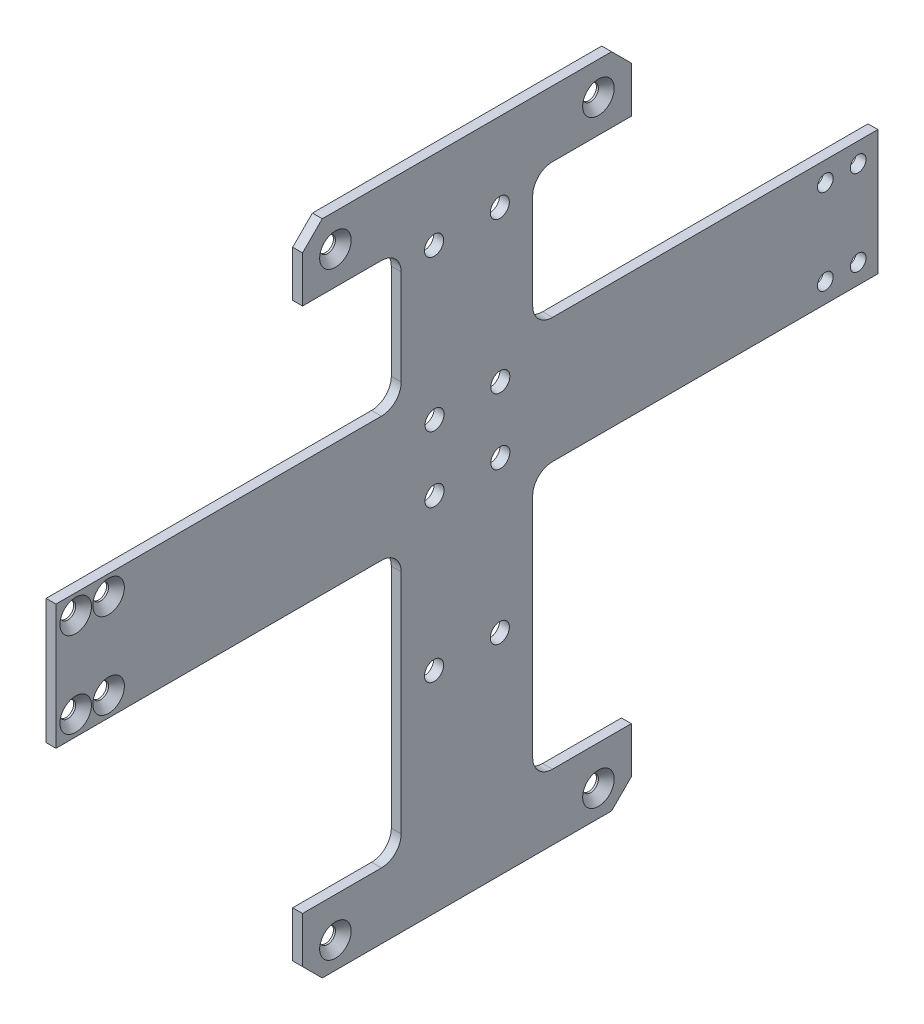
SolidWorks part; units mm, degrees
material "Hexcel AS4C (3000 Filaments)"
ref_plane "Front Plane" through (0, 0, 0) normal (0, 0, 1) x (1, 0, 0)
ref_plane "Top Plane" through (0, 0, 0) normal (0, 1, 0) x (1, 0, 0)
ref_plane "Right Plane" through (0, 0, 0) normal (1, 0, 0) x (0, 0, -1)
sketch "Sketch1" plane through (0, 0, 0) normal (0, 0, 1) x (1, 0, 0)
  line L1 (0.75, -12.5) -> (-0.75, -12.5)
  line L2 (0.75, -12.5) -> (0.75, 12.5)
  line L3 (0.75, 12.5) -> (-0.75, 12.5)
  line L4 (-0.75, -12.5) -> (-0.75, 12.5)
  line L5 (0.75, -12.5) -> (-0.75, 12.5) construction
  line L6 (0.75, 12.5) -> (-0.75, -12.5) construction
  point P0 (0, 0)
  dimension "D1" = 1.5
  dimension "D2" = 25
extrude "Boss-Extrude1" add sketch "Sketch1" along normal blind 73 and the other way blind 73
fillet "Fillet1" radius 1 4 edges at (0, -12.5, 73) (0, 12.5, 73) (0, -12.5, -73) (0, 12.5, -73)
sketch "Sketch10" plane through (0, 0, 0) normal (1, 0, 0) x (0, 0, -1)
  line L0 (72, 12.5) -> (-72, 12.5) construction
  line L1 (-10, 12.5) -> (10, 12.5)
  line L2 (-10, 12.5) -> (-10, 37.5)
  line L3 (-10, 37.5) -> (10, 37.5)
  line L4 (10, 12.5) -> (10, 37.5)
  line L5 (0, 0) -> (0, 37.5) construction
  dimension "D1" = 20
  dimension "D2" = 25
extrude "Boss-Extrude2" add sketch "Sketch10" along normal up to surface and the other way up to surface up to face at (0.75, 0, 0) other way up to face at (-0.75, 0, 0)
sketch "Sketch16" plane through (-0.75, 0, 0) normal (-1, 0, 0) x (0, 0, 1)
  line L0 (-72, 12.5) -> (-10, 12.5) construction
  line L1 (-73, 9.5) -> (-32.5, 9.5)
  line L2 (-73, 9.5) -> (-73, 12.5)
  line L3 (-73, 12.5) -> (-32.5, 12.5)
  line L4 (-32.5, 9.5) -> (-32.5, 12.5)
  line L5 (-73, 11.5) -> (-73, -11.5) construction
  line L6 (0, 0) -> (-20.9009, 0) construction
  line L7 (-32.5, -9.5) -> (-32.5, -12.5)
  line L8 (-73, -12.5) -> (-32.5, -12.5)
  line L9 (-73, -9.5) -> (-73, -12.5)
  line L10 (-73, -9.5) -> (-32.5, -9.5)
  dimension "D1" = 19
  dimension "D2" = 40.5
extrude "Cut-Extrude2" cut sketch "Sketch16" against normal blind 10
mirror "Mirror3" about plane through (0, 0, 0) normal (0, 0, 1) of "Cut-Extrude2"
sketch "Sketch21" plane through (0.75, 0, 0) normal (1, 0, 0) x (0, 0, -1)
  line L0 (10, 37.5) -> (-10, 37.5) construction
  line L1 (32.5, -12.5) -> (-32.5, -12.5)
  line L2 (32.5, -12.5) -> (32.5, -59.5)
  line L3 (32.5, -59.5) -> (-32.5, -59.5)
  line L4 (-32.5, -12.5) -> (-32.5, -59.5)
  line L5 (32.5, -12.5) -> (-32.5, -59.5) construction
  line L6 (32.5, -59.5) -> (-32.5, -12.5) construction
  point P0 (0, -36)
  dimension "D1" = 97
extrude "Boss-Extrude4" add sketch "Sketch21" against normal up to surface (1.5 mm away) up to face at (-0.75, 6.25, 0)
fillet "Fillet4" radius 1.5 4 edges at (0, -9.5, -73) (0, 9.5, -73) (0, -9.5, 73) (0, 9.5, 73)
sketch "Sketch17" plane through (-0.75, 0, 0) normal (-1, 0, 0) x (0, 0, 1)
  line L0 (0, 0) -> (0, 46.0234) construction
  line L1 (-10, 37.5) -> (-32.5, 37.5)
  line L2 (-10, 37.5) -> (-10, 12.5)
  line L3 (-10, 12.5) -> (-32.5, 12.5)
  line L4 (-32.5, 37.5) -> (-32.5, 12.5)
  line L5 (-10, 37.5) -> (-32.5, 12.5) construction
  line L6 (-10, 12.5) -> (-32.5, 37.5) construction
  line L7 (10, 12.5) -> (32.5, 37.5) construction
  line L8 (10, 37.5) -> (32.5, 12.5) construction
  line L9 (32.5, 37.5) -> (32.5, 12.5)
  line L10 (10, 12.5) -> (32.5, 12.5)
  line L11 (10, 37.5) -> (10, 12.5)
  line L12 (10, 37.5) -> (32.5, 37.5)
  point P0 (-21.25, 25)
  point P14 (21.25, 25)
extrude "Boss-Extrude3" add sketch "Sketch17" against normal up to surface (1.5 mm away) up to face at (0.75, 0.3, 0)
hole_wizard "M2 Clearance Hole4" positions "Sketch19" profile "Sketch18" hole size "M2" standard "DIN"
sketch "Sketch19" plane through (0.75, 0, 0) normal (1, 0, 0) x (0, 0, -1)
  line L0 (0, 0) -> (0, 45.1991) construction
  line L2 (32.5, 37.5) -> (-32.5, 37.5) construction
  point P0 (20, 35)
  point P10 (-20, 35)
  point P13 (-20, -56)
  point P15 (20, -56)
  dimension "D1" = 2.5
  dimension "D2" = 40
  dimension "D3" = 91
sketch "Sketch18" plane through (0.75, 35, -20) normal (0, 1, 0) x (0, 0, -1)
  line L0 (0, 0) -> (0, 1.5)
  line L1 (0, 1.5) -> (1.2, 1.5)
  line L2 (1.2, 1.5) -> (1.2, 0)
  line L5 (1.2, 0) -> (0, 0)
  line L10 (0, 1.5) -> (-1.2, 1.5) construction
  line L11 (0, -6.35) -> (0, 107.95) construction
  dimension "Hole Dia." = 2.4
  dimension "Hole Depth" = 1.5
  dimension "Drill Angle" = 180
sketch "Sketch22" plane through (-0.75, 0, 0) normal (-1, 0, 0) x (0, 0, 1)
  line L0 (32.5, -59.5) -> (-32.5, -59.5) construction
  line L1 (62.5, -59.5) -> (-62.5, -59.5)
  line L2 (62.5, -59.5) -> (62.5, 59.5)
  line L3 (62.5, 59.5) -> (-62.5, 59.5)
  line L4 (-62.5, -59.5) -> (-62.5, 59.5)
  line L5 (62.5, -59.5) -> (-62.5, 59.5) construction
  line L6 (62.5, 59.5) -> (-62.5, -59.5) construction
  point P0 (0, 0)
  dimension "D1" = 125
extrude "Cut-Extrude4" cut sketch "Sketch22" against normal blind 10 flip side to cut
hole_wizard "M2 Clearance Hole5" positions "Sketch24" profile "Sketch23" hole size "M2" standard "DIN"
sketch "Sketch24" plane through (0.75, 0, 0) normal (1, 0, 0) x (0, 0, -1)
  line L1 (-54.5, -6.5) -> (-59.5, -6.5)
  line L2 (-54.5, -6.5) -> (-54.5, 6.5)
  line L3 (-54.5, 6.5) -> (-59.5, 6.5)
  line L4 (-59.5, -6.5) -> (-59.5, 6.5)
  line L5 (-54.5, -6.5) -> (-59.5, 6.5) construction
  line L6 (-54.5, 6.5) -> (-59.5, -6.5) construction
  line L7 (-54.5, 0) -> (0, 0) construction
  point P0 (-54.5, -6.5)
  point P9 (-54.5, 6.5)
  point P11 (-59.5, 6.5)
  point P13 (-59.5, -6.5)
  dimension "D1" = 13
  dimension "D2" = 5
  dimension "D3" = 54.5
sketch "Sketch23" plane through (0.75, -6.5, 54.5) normal (0, 1, 0) x (0, 0, -1)
  line L0 (0, 0) -> (0, 11.5)
  line L1 (0, 11.5) -> (1.2, 11.5)
  line L2 (1.2, 11.5) -> (1.2, 0)
  line L5 (1.2, 0) -> (0, 0)
  line L10 (0, 11.5) -> (-1.2, 11.5) construction
  line L11 (0, -6.35) -> (0, 107.95) construction
  dimension "Hole Dia." = 2.4
  dimension "Hole Depth" = 11.5
  dimension "Drill Angle" = 180
mirror "Mirror4" about plane through (0, 0, 0) normal (0, 0, 1) of "M2 Clearance Hole5"
sketch "Sketch25" plane through (0.75, 0, 0) normal (1, 0, 0) x (0, 0, -1)
  line L1 (-32.5, 37.5) -> (32.5, 37.5)
  line L2 (-32.5, 37.5) -> (-32.5, 40)
  line L3 (-32.5, 40) -> (32.5, 40)
  line L4 (32.5, 37.5) -> (32.5, 40)
  line L5 (-32.5, -59.5) -> (32.5, -59.5)
  line L6 (-32.5, -59.5) -> (-32.5, -60)
  line L7 (-32.5, -60) -> (32.5, -60)
  line L8 (32.5, -59.5) -> (32.5, -60)
  dimension "D1" = 2.5
  dimension "D2" = 0.5
extrude "Boss-Extrude5" add sketch "Sketch25" against normal up to surface (1.5 mm away) up to face at (-0.75, -6.5, -53.3)
hole_wizard "M2.5 Clearance Hole1" positions "Sketch27" profile "Sketch26" hole size "M2.5" standard "DIN"
sketch "Sketch27" plane through (0.75, 0, 0) normal (1, 0, 0) x (0, 0, -1)
  line L2 (5, -28) -> (-5, -28)
  line L3 (5, -28) -> (5, 28)
  line L4 (5, 28) -> (-5, 28)
  line L5 (-5, -28) -> (-5, 28)
  line L6 (5, -28) -> (-5, 28) construction
  line L7 (5, 28) -> (-5, -28) construction
  line L8 (0, -28) -> (0, 0) construction
  line L9 (32.5, 40) -> (-32.5, 40) construction
  line L10 (-32.5, -60) -> (32.5, -60) construction
  point P0 (-5, -28)
  point P298 (5, -28)
  point P300 (5, 28)
  point P302 (-5, 28)
  dimension "D1" = 10
  dimension "D2" = 12
  dimension "D3" = 32
sketch "Sketch26" plane through (0.75, -28, 5) normal (0, 1, 0) x (0, 0, -1)
  line L0 (0, 0) -> (0, 11.5)
  line L1 (0, 11.5) -> (1.45, 11.5)
  line L2 (1.45, 11.5) -> (1.45, 0)
  line L5 (1.45, 0) -> (0, 0)
  line L10 (0, 11.5) -> (-1.45, 11.5) construction
  line L11 (0, -6.35) -> (0, 107.95) construction
  dimension "Hole Dia." = 2.9
  dimension "Hole Depth" = 11.5
  dimension "Drill Angle" = 180
sketch "Sketch29" plane through (0.75, 0, 0) normal (1, 0, 0) x (0, 0, -1)
  line L0 (-32.5, 9.5) -> (-62.5, 9.5) construction
  line L1 (-32.5, 40) -> (-25, 40)
  line L2 (-32.5, 40) -> (-32.5, 9.5)
  line L3 (-32.5, 9.5) -> (-25, 9.5)
  line L4 (-25, 40) -> (-25, 9.5)
  line L5 (0, 0) -> (0, 45.0384) construction
  line L6 (-32.5, -60) -> (32.5, -60) construction
  line L7 (-32.5, -9.5) -> (-25, -9.5)
  line L8 (-32.5, -9.5) -> (-32.5, -60)
  line L9 (-32.5, -60) -> (-25, -60)
  line L10 (-25, -9.5) -> (-25, -60)
  line L11 (25, -9.5) -> (25, -60)
  line L12 (32.5, -60) -> (25, -60)
  line L13 (32.5, -9.5) -> (32.5, -60)
  line L14 (32.5, -9.5) -> (25, -9.5)
  line L15 (25, 40) -> (25, 9.5)
  line L16 (32.5, 9.5) -> (25, 9.5)
  line L17 (32.5, 40) -> (32.5, 9.5)
  line L18 (32.5, 40) -> (25, 40)
  dimension "D1" = 50
extrude "Cut-Extrude5" cut sketch "Sketch29" against normal blind 10
sketch "Sketch31" plane through (0.75, 0, 0) normal (1, 0, 0) x (0, 0, -1)
  line L0 (0, 0) -> (0, 43.4497) construction
  line L1 (-25, 9.5) -> (-10, 9.5)
  line L2 (-25, 9.5) -> (-25, 30)
  line L3 (-25, 30) -> (-10, 30)
  line L4 (-10, 9.5) -> (-10, 30)
  line L5 (25, 40) -> (-25, 40) construction
  line L6 (-25, -9.5) -> (-10, -9.5)
  line L7 (-25, -9.5) -> (-25, -50)
  line L8 (-25, -50) -> (-10, -50)
  line L9 (-10, -9.5) -> (-10, -50)
  line L10 (10, -9.5) -> (10, -50)
  line L11 (25, -50) -> (10, -50)
  line L12 (25, -9.5) -> (25, -50)
  line L13 (25, -9.5) -> (10, -9.5)
  line L14 (10, 9.5) -> (10, 30)
  line L15 (25, 30) -> (10, 30)
  line L16 (25, 9.5) -> (25, 30)
  line L17 (25, 9.5) -> (10, 9.5)
  line L18 (-25, -60) -> (-25, -9.5) construction
  line L19 (-25, -60) -> (25, -60) construction
  dimension "D3" = 20
  dimension "D1" = 10
  dimension "D2" = 10
extrude "Cut-Extrude7" cut sketch "Sketch31" against normal blind 10
fillet "Fillet5" radius 3 8 edges at (0, 9.5, -10) (0, 30, -10) (0, 30, 10) (0, 9.5, 10) (0, -9.5, 10) (0, -9.5, -10) (0, -50, -10) (0, -50, 10)
chamfer "Chamfer1" distance 1.2 angle 45 8 edges at (0.75, -6.5, 53.3) (0.75, -6.5, 58.3) (0.75, 6.5, 58.3) (0.75, 6.5, 53.3) (0.75, -56, 18.8) (0.75, -56, -21.2) (0.75, 35, -21.2) (0.75, 35, 18.8)
chamfer "Chamfer2" distance 3 angle 45 4 edges at (0, -60, 25) (0, -60, -25) (0, 40, 25) (0, 40, -25)
sketch "Sketch32" plane through (0.75, 0, 0) normal (1, 0, 0) x (0, 0, -1)
  point P0 (-4.925, 5)
  point P1 (5.075, 5)
  point P2 (5.075, -5)
  point P3 (-4.925, -5)
hole_wizard "M2.5 Clearance Hole2" positions "Sketch34" profile "Sketch33" hole size "M2.5" standard "DIN"
sketch "Sketch34" plane through (-0.75, 0, 0) normal (-1, 0, 0) x (0, 0, 1)
  point P0 (-5.075, -5)
  point P1 (4.925, -5)
  point P3 (-5.075, 5)
  point P5 (4.925, 5)
sketch "Sketch33" plane through (-0.75, -5, -5.075) normal (0, 1, 0) x (0, 0, 1)
  line L0 (0, 0) -> (0, 10)
  line L1 (0, 10) -> (1.45, 10)
  line L2 (1.45, 10) -> (1.45, 0)
  line L5 (1.45, 0) -> (0, 0)
  line L10 (0, 10) -> (-1.45, 10) construction
  line L11 (0, -6.35) -> (0, 107.95) construction
  dimension "Hole Dia." = 2.9
  dimension "Hole Depth" = 10
  dimension "Drill Angle" = 180
